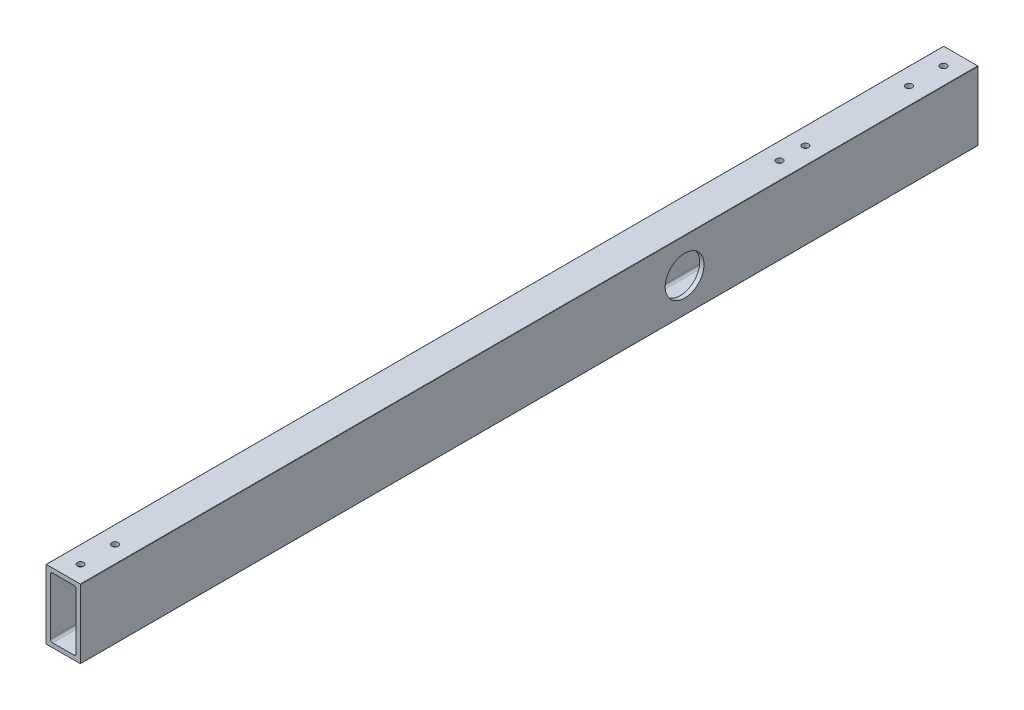
SolidWorks part; units mm, degrees
material "1060 Alloy"
ref_plane "Front Plane" through (0, 0, 0) normal (0, 0, 1) x (1, 0, 0)
ref_plane "Top Plane" through (0, 0, 0) normal (0, 1, 0) x (1, 0, 0)
ref_plane "Right Plane" through (0, 0, 0) normal (1, 0, 0) x (0, 0, -1)
ref_plane "Plane1" through (0, 0, 0) normal (0, 0, -1) x (-1, 0, 0)
sketch "Sketch1" plane through (0, 0, 0) normal (0, 0, -1) x (-1, 0, 0)
  line L0 (-3.175, 46.0375) -> (-3.175, 4.7625)
  line L1 (-4.7625, 3.175) -> (-20.6375, 3.175)
  line L2 (-22.225, 4.7625) -> (-22.225, 46.0375)
  line L3 (-20.6375, 47.625) -> (-4.7625, 47.625)
  line L4 (0, 0.254) -> (0, 50.546)
  line L5 (-0.254, 50.8) -> (-25.146, 50.8)
  line L6 (-25.4, 50.546) -> (-25.4, 0.254)
  line L7 (-25.146, 0) -> (-0.254, 0)
  arc A0 (-3.175, 4.7625) -> (-4.7625, 3.175) centre (-4.7625, 4.7625) cw
  arc A1 (-20.6375, 3.175) -> (-22.225, 4.7625) centre (-20.6375, 4.7625) cw
  arc A2 (-22.225, 46.0375) -> (-20.6375, 47.625) centre (-20.6375, 46.0375) cw
  arc A3 (-4.7625, 47.625) -> (-3.175, 46.0375) centre (-4.7625, 46.0375) cw
  arc A4 (-0.254, 0) -> (0, 0.254) centre (-0.254, 0.254) ccw
  arc A5 (0, 50.546) -> (-0.254, 50.8) centre (-0.254, 50.546) ccw
  arc A6 (-25.146, 50.8) -> (-25.4, 50.546) centre (-25.146, 50.546) ccw
  arc A7 (-25.4, 0.254) -> (-25.146, 0) centre (-25.146, 0.254) ccw
extrude "Boss-Extrude1" add sketch "Sketch1" against normal blind 660.4
sketch "Sketch2" plane through (0, 50.8, 0) normal (0, 1, 0) x (1, 0, 0)
  line L0 (0.254, -660.4) -> (25.146, -660.4) construction
  line L1 (25.146, -330.2) -> (0, -330.2) construction
  line L2 (25.146, -660.4) -> (25.146, 0) construction
  line L3 (0, -660.4) -> (0, 0) construction
  circle A0 centre (12.7, -647.7) radius 2.3813
  circle A1 centre (12.7, -622.3) radius 2.3813
  circle A2 centre (12.7, -38.1) radius 2.3812
  circle A3 centre (12.7, -12.7) radius 2.3813
  circle A4 centre (12.7, -133.35) radius 2.3813
  circle A5 centre (12.7, -114.3) radius 2.3813
  dimension "D1" = 4.7625
  dimension "D2" = 4.7625
  dimension "D3" = 12.7
  dimension "D4" = 25.4
  dimension "D6" = 4.7625
  dimension "D7" = 4.7625
  dimension "D5" = 76.2
  dimension "D8" = 19.05
extrude "Cut-Extrude1" cut sketch "Sketch2" against normal through all
sketch "Sketch5" plane through (25.4, 0, 0) normal (1, 0, 0) x (0, 0, -1)
  line L0 (-660.4, 50.546) -> (0, 50.546) construction
  line L2 (0, 50.546) -> (0, 0.254) construction
  circle A0 centre (-215.9, 25.146) radius 14.2875
  dimension "D1" = 28.575
  dimension "D2" = 25.4
  dimension "D3" = 215.9
extrude "Cut-Extrude2" cut sketch "Sketch5" against normal through all
